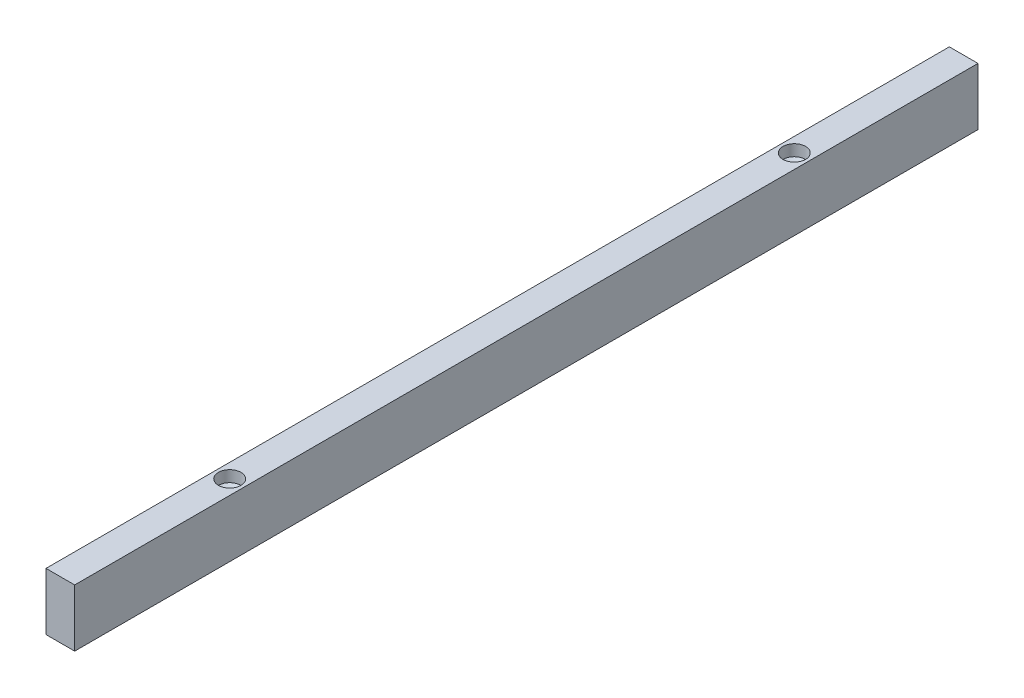
SolidWorks part; units mm, degrees
material "PC High Viscosity"
ref_plane "Front Plane" through (0, 0, 0) normal (0, 0, 1) x (1, 0, 0)
ref_plane "Top Plane" through (0, 0, 0) normal (0, 1, 0) x (1, 0, 0)
ref_plane "Right Plane" through (0, 0, 0) normal (1, 0, 0) x (0, 0, -1)
sketch "Sketch1" plane through (0, 0, 0) normal (0, 0, 1) x (1, 0, 0)
  line L0 (0, 0) -> (0, 12.7) construction
  line L1 (6.35, -12.7) -> (-6.35, -12.7)
  line L2 (6.35, -12.7) -> (6.35, 12.7)
  line L3 (6.35, 12.7) -> (-6.35, 12.7)
  line L4 (-6.35, -12.7) -> (-6.35, 12.7)
  line L5 (0, 0) -> (6.35, 0) construction
  dimension "D1" = 25.4
  dimension "D2" = 12.7
extrude "Boss-Extrude1" add sketch "Sketch1" along normal blind 200 and the other way blind 200
sketch "Sketch2" plane through (0, 0, 0) normal (1, 0, 0) x (0, 0, -1)
  line L0 (-125, -12.7) -> (-125, 55.0486) construction
  line L1 (-125, 12.7) -> (-120, 12.7)
  line L2 (-122, 6.5453) -> (-122, -2.3)
  line L3 (-122, -2.3) -> (-123.35, -3.0794)
  line L4 (-123.35, -3.0794) -> (-123.35, -12.7)
  line L5 (-212.738, -12.7) -> (210.6836, -12.7) construction
  line L6 (-123.35, -12.7) -> (-125, -12.7)
  line L7 (-125, -12.7) -> (-125, 12.7)
  line L8 (200, 12.7) -> (-200, 12.7) construction
  line L9 (-122, 6.5453) -> (-120, 7.7)
  line L10 (-120, 7.7) -> (-120, 12.7)
  dimension "D1" = 10
  dimension "D2" = 3.3
  dimension "D3" = 60
  dimension "D4" = 6
  dimension "D5" = 10
  dimension "D6" = 5
revolve "Cut-Revolve1" cut sketch "Sketch2" angle 360 about L0
mirror "Mirror1" about plane through (0, 0, 0) normal (0, 0, 1) of "Cut-Revolve1"
